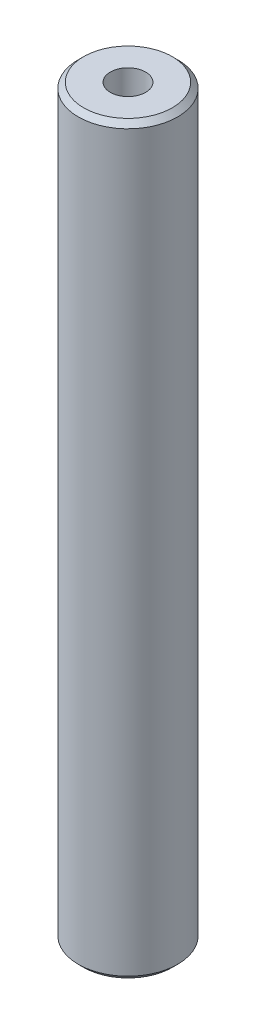
SolidWorks part; units mm, degrees
ref_plane "Front Plane" through (0, 0, 0) normal (0, 0, 1) x (1, 0, 0)
ref_plane "Top Plane" through (0, 0, 0) normal (0, 1, 0) x (1, 0, 0)
ref_plane "Right Plane" through (0, 0, 0) normal (1, 0, 0) x (0, 0, -1)
sketch "Sketch1" plane through (0, 0, 0) normal (0, 1, 0) x (1, 0, 0)
  circle A0 centre (0, 0) radius 40
  dimension "SHAFT_OD" = 80
extrude "Boss-Extrude1" add sketch "Sketch1" along normal blind 600
sketch "Sketch2" plane through (0, 0, 0) normal (0, 1, 0) x (1, 0, 0)
  circle A0 centre (0, 0) radius 14.2353
  dimension "BORE_D" = 28.4705
extrude "Cut-Extrude1" cut sketch "Sketch2" along normal through all
chamfer "Chamfer1" distance 4.2585 angle 45.024 2 edges at (0, 600, 40) (0, 0, 40) first distance on face at (0, 600, 40) first distance on face at (0, 0, 14.2353)
